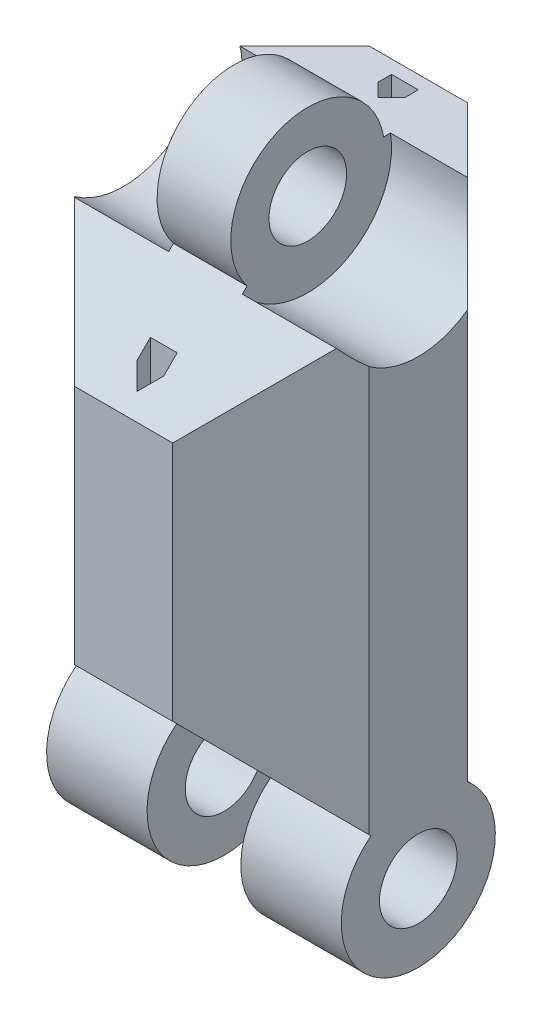
SolidWorks part; units mm, degrees
ref_plane "Front Plane" through (0, 0, 0) normal (0, 0, 1) x (1, 0, 0)
ref_plane "Top Plane" through (0, 0, 0) normal (0, 1, 0) x (1, 0, 0)
ref_plane "Right Plane" through (0, 0, 0) normal (1, 0, 0) x (0, 0, -1)
sketch "Sketch1" plane through (0, 0, 0) normal (0, 1, 0) x (1, 0, 0)
  line L0 (-1.8333, -5.5) -> (1.8333, -5.5)
  line L1 (1.8333, -5.5) -> (5.5, -1.8333)
  line L2 (5.5, -1.8333) -> (5.5, 1.8333)
  line L3 (5.5, 1.8333) -> (1.8333, 5.5)
  line L4 (1.8333, 5.5) -> (-1.8333, 5.5)
  line L5 (-1.8333, 5.5) -> (-5.5, 1.8333)
  line L6 (-5.5, 1.8333) -> (-5.5, -1.8333)
  line L7 (-5.5, -1.8333) -> (-1.8333, -5.5)
  point P16 (5.5, 0)
  point P19 (0, -5.5)
  dimension "D1" = 135
  dimension "D2" = 11
  dimension "D3" = 11
  dimension "D4" = 3.6667
extrude "Boss-Extrude1" add sketch "Sketch1" along normal blind 20
sketch "Sketch2" plane through (0, 0, 0) normal (1, 0, 0) x (0, 0, -1)
  line L0 (0, 20) -> (-5.5, 20)
  line L1 (-1.8333, 20) -> (1.8333, 20) construction
  line L2 (-5.5, 20) -> (-5.5, 14.5)
  line L3 (-5.5, 20) -> (-5.5, 0) construction
  line L4 (-5.5, 14.5) -> (0, 20)
  line L5 (0, 0) -> (-5.5, 0)
  line L6 (-1.8333, 0) -> (1.8333, 0) construction
  line L7 (-5.5, 0) -> (-5.5, 5.5)
  line L8 (-5.5, 5.5) -> (0, 0)
  dimension "D1" = 45
  dimension "D2" = 45
extrude "Cut-Extrude1" cut sketch "Sketch2" against normal through all both and the other way through all contours L4 L0 L2 | L8 L5 L7
sketch "Sketch3" plane through (0, 0, 0) normal (0, 1, 0) x (1, 0, 0)
  line L0 (0, -5) -> (-0.5, -4.5)
  line L1 (-0.5, -4.5) -> (-0.5, -4)
  line L2 (-0.5, -4) -> (0.5, -4)
  line L3 (0.5, -4) -> (0.5, -4.5)
  line L4 (0.5, -4.5) -> (0, -5)
  line L5 (-1.8333, -5.5) -> (1.8333, -5.5) construction
  line L6 (0.5, 5) -> (0.5, 4.5)
  line L7 (-0.5, 5) -> (0.5, 5)
  line L8 (-0.5, 4.5) -> (-0.5, 5)
  line L9 (0, 4) -> (-0.5, 4.5)
  line L10 (0.5, 4.5) -> (0, 4)
  line L11 (1.8333, 5.5) -> (-1.8333, 5.5) construction
  point P6 (0, -4)
  point P13 (0, -5.5)
  dimension "D1" = 1
  dimension "D2" = 0.5
  dimension "D3" = 0.5
  dimension "D4" = 0.5
  dimension "D5" = 0.5
  dimension "D6" = 2
  dimension "D7" = 0.5
extrude "Cut-Extrude2" cut sketch "Sketch3" along normal through all
sketch "Sketch4" plane through (0, 0, 0) normal (1, 0, 0) x (0, 0, -1)
  circle A0 centre (0, 19.5) radius 2.875
  dimension "D2" = 5.75
  dimension "D1" = 0.5
extrude "Boss-Extrude2" add sketch "Sketch4" along normal mid plane 2.75
sketch "Sketch5" plane through (1.375, 0, 0) normal (1, 0, 0) x (0, 0, -1)
  circle A0 centre (0, 19.5) radius 3.125
  dimension "D1" = 6.25
extrude "Cut-Extrude3" cut sketch "Sketch5" along normal through all
mirror "Mirror1" about plane through (0, 0, 0) normal (1, 0, 0) of "Cut-Extrude3"
sketch "Sketch6" plane through (0, 0, 0) normal (1, 0, 0) x (0, 0, -1)
  circle A0 centre (0, -0.5) radius 3.125
  dimension "D2" = 6.25
  dimension "D1" = 0.5
extrude "Cut-Extrude4" cut sketch "Sketch6" against normal mid plane 3.5
sketch "Sketch7" plane through (-1.75, 0, 0) normal (1, 0, 0) x (0, 0, -1)
  circle A0 centre (0, -0.5) radius 2.875
  dimension "D2" = 5.75
  dimension "D1" = 0.5
extrude "Boss-Extrude3" add sketch "Sketch7" against normal up to surface (3.75 mm away) up to face at (-5.5, 7.0355, 0)
sketch "Sketch8" plane through (1.75, 0, 0) normal (-1, 0, 0) x (0, 0, 1)
  circle A0 centre (0, -0.5) radius 2.875
  dimension "D2" = 5.75
  dimension "D1" = 0.5
extrude "Boss-Extrude4" add sketch "Sketch8" against normal up to surface (3.75 mm away) up to face at (5.5, 7.0355, 0)
sketch "Sketch10" plane through (1.375, 0, 0) normal (1, 0, 0) x (0, 0, -1)
  circle A0 centre (0, 19.5) radius 1.45
  dimension "D1" = 2.9
extrude "Cut-Extrude5" cut sketch "Sketch10" against normal through all both and the other way through all
sketch "Sketch11" plane through (5.5, 0, 0) normal (1, 0, 0) x (0, 0, -1)
  circle A0 centre (0, -0.5) radius 1.45
  dimension "D1" = 2.9
extrude "Cut-Extrude6" cut sketch "Sketch11" against normal through all both and the other way through all
